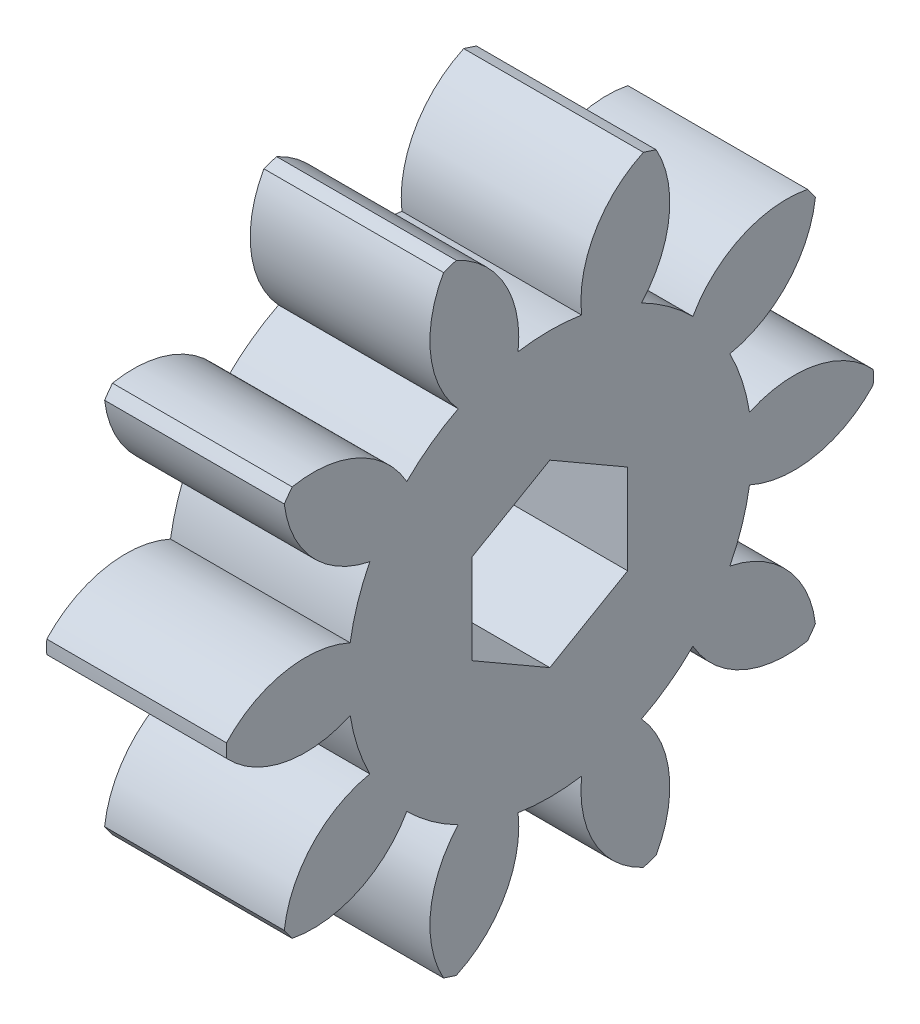
SolidWorks part; units mm, degrees
ref_plane "Plane1" through (0, 0, 0) normal (0, 0, 1) x (1, 0, 0)
ref_plane "Plane2" through (0, 0, 0) normal (0, 1, 0) x (1, 0, 0)
ref_plane "Plane3" through (0, 0, 0) normal (1, 0, 0) x (0, 0, -1)
sketch "HoldingSke" plane through (0, 0, 0) normal (0, 1, 0) x (1, 0, 0)
  line L0 (0, 0) -> (0.6565, -0.1158)
  line L1 (-15, 0) -> (100, 0) construction
  line L2 (0, 0) -> (-2.1039, 2.3779)
  line L3 (0, 0) -> (-11.863, 4.5341)
  line L4 (0, 0) -> (8.5048, 1.4996)
  line L5 (0, 0) -> (-46.8476, -17.4728)
  line L6 (0, 0) -> (-9.9476, -6.7116)
  line L7 (-2.1039, 2.3779) -> (8.6586, 51.206)
  line L8 (-76.2, 54.61) -> (-75.3, 54.61)
  line L9 (-71.009, 38.7566) -> (-53.1078, 45.2721)
  line L10 (-76.2, 71.12) -> (104.1128, 71.12)
  line L11 (0, 0) -> (-12, 0)
  line L12 (-76.2, 101.6) -> (-76.147, 101.6)
  line L13 (24.9733, 27.94) -> (52.9518, 28.4284)
  line L14 (24.9733, 27.94) -> (24.9743, 27.94)
  line L15 (24.9733, 27.94) -> (100.4006, 29.5858)
  line L16 (-63.627, -1.5) -> (-12.827, -1.5)
  circle A0 centre (0, 0) radius 2.5
  circle A1 centre (0, 0) radius 5.624
  circle A2 centre (0, 0) radius 37.5
  circle A3 centre (0, 0) radius 2.5
  dimension "MHD" = 11.248
  dimension "Hub_dia" = 75
  dimension "Bore" = 5
  dimension "MBD" = 5
  dimension "Num_teeth" = 10
  dimension "Pitch" = 0.6667
  dimension "Overall_len" = 50
  dimension "Show_teeth" = 10
  dimension "Thickness" = 12
  dimension "OAL" = 50.0002
  dimension "T_dim" = 0.9
  dimension "Ap" = 20
  dimension "H" = 19.05
  dimension "Pitch_radius" = 180.3128
  dimension "Width" = 12
  dimension "Backlash" = 0.053
  dimension "Addendum_fac" = 1
  dimension "Dedendum_fac" = 1.25
  dimension "Clearance_fac" = 0.25
  dimension "Dedendum_add" = 0.001
  dimension "Module" = 1.5
sketch "BasProSke" plane through (0, 0, 0) normal (0, 1, 0) x (1, 0, 0)
  line L0 (-10, 0) -> (60, 0) construction
  line L1 (0, 0) -> (0, 9)
  line L2 (0, 0) -> (5, 0)
  line L3 (5, 0) -> (5, 9)
  line L4 (5, 9) -> (0, 9)
  dimension "Thickness" = 5
  dimension "Diameter" = 18
revolve "Base-Revolve" add sketch "BasProSke" angle 360 about L0
sketch "TooCutSke" plane through (0, 0, 0) normal (1, 0, 0) x (0, 0, -1)
  line L1 (0, 0) -> (0, 107) construction
  line L2 (0, 0) -> (-1.2658, 7.3924) construction
  line L3 (0, 0) -> (-4.5869, 14.117) construction
  line L4 (-1.2658, 7.3924) -> (-2.2934, 7.0585) construction
  arc A0 (0.8839, 5.5541) -> (-0.8839, 5.5541) centre (0, 0) ccw
  arc A1 (2.6378, 8.6313) -> (-2.6378, 8.6313) centre (0, 0) ccw
  circle A2 centre (0, 0) radius 7.5 construction
  circle A3 centre (0, 0) radius 7.0477 construction
  arc A4 (-0.8839, 5.5541) -> (-2.6378, 8.6313) centre (-3.8646, 5.8936) ccw
  arc A5 (2.6378, 8.6313) -> (0.8839, 5.5541) centre (3.8646, 5.8936) ccw
  dimension "Root_dia" = 11.248
  dimension "Overcut_dia" = 18.0508
  dimension "Pitch_dia" = 15
  dimension "Base_dia" = 14.0954
  dimension "Flank_rad" = 3
  dimension "Half_ang" = 18
  dimension "Half_CT" = 1.0805
extrude "ToothCut" cut sketch "TooCutSke" along normal through all
fillet "Breaks" [suppressed] radius 0.03 tangent propagation no
fillet "RootFillets" [suppressed] radius 0.376
pattern_circular "TeethCuts" count 10 every 36 about axis through (-10, 0, 0) along (1, 0, 0) of "ToothCut", "RootFillets", "Breaks"
sketch "HubNeaOneSke" plane through (0, 0, 0) normal (-1, 0, 0) x (0, 0, 1)
  circle A0 centre (0, 0) radius 5.624
  dimension "Diameter" = 11.248
extrude "HubNearOne" [suppressed] add sketch "HubNeaOneSke" along normal blind 45.0002
sketch "HubNeaBotSke" plane through (0, 0, 0) normal (-1, 0, 0) x (0, 0, 1)
  circle A0 centre (0, 0) radius 5.624
  dimension "Diameter" = 11.248
extrude "HubNearBoth" [suppressed] add sketch "HubNeaBotSke" along normal blind 22.5001
ref_plane "FarPln" through (5, 0, 0) normal (1, 0, 0) x (0, 0, -1)
sketch "HubFarSke" plane through (5, 0, 0) normal (1, 0, 0) x (0, 0, -1)
  circle A0 centre (0, 0) radius 5.624
  dimension "Diameter" = 11.248
extrude "HubFar" [suppressed] add sketch "HubFarSke" along normal blind 22.5001
sketch "BorSke" plane through (0, 0, 0) normal (1, 0, 0) x (0, 0, -1)
  line L1 (0, 2.5) -> (-2.1651, 1.25)
  line L2 (-2.1651, 1.25) -> (-2.1651, -1.25)
  line L3 (-2.1651, -1.25) -> (0, -2.5)
  line L4 (0, -2.5) -> (2.1651, -1.25)
  line L5 (2.1651, -1.25) -> (2.1651, 1.25)
  line L6 (2.1651, 1.25) -> (0, 2.5)
  circle A0 centre (0, 0) radius 2.5 construction
  circle A1 centre (0, 0) radius 2.1651 construction
  point P2 (-0.1277, 3.0777)
  point P11 (0, 2.5)
  dimension "Diameter" = 5
extrude "Bore" cut sketch "BorSke" along normal mid plane 100.0004
sketch "KeySke" plane through (0, 0, 0) normal (1, 0, 0) x (0, 0, -1)
  line L0 (-1, 0) -> (-1, 3.4)
  line L1 (-1, 3.4) -> (1, 3.4)
  line L2 (1, 3.4) -> (1, 0)
  line L3 (0, 0) -> (0, 34) construction
  line L4 (-1, 0) -> (1, 0)
  dimension "Offset" = 3.4
  dimension "Width" = 2
extrude "Keyway" [suppressed] cut sketch "KeySke" along normal mid plane 100.0004
pattern_circular "Keyway2" [suppressed] count 2 every 90 about axis through (-10, 0, 0) along (1, 0, 0) reverse direction yes
equation "' \"Module@HoldingSke\" = 6.35"
equation "' \"Num_teeth@HoldingSke\" = 12"
equation "' \"Ap@HoldingSke\" =  20"
equation "' \"Ap@HoldingSke\" = 20"
equation "' \"Width@HoldingSke\" = 0.5 * 25.4"
equation "' \"Hub_dia@HoldingSke\"= 1 * 25.4"
equation "' \"Hub_dia@HoldingSke\" = 1 * 25.4"
equation "' \"Overall_len@HoldingSke\" = 1.0 * 25.4"
equation "' \"Bore@HoldingSke\" = 0.75 * 25.4"
equation "' \"T_dim@HoldingSke\" = 0.1 * 25.4"
equation "' \"Width@KeySke\" = 0.25 * 25.4"
equation "' \"Show_teeth@HoldingSke\" = 13"
equation "' \"Backlash@HoldingSke\" = 0.009 * 25.4"
equation "' \"Addendum_fac@HoldingSke\" = 1.0"
equation "' \"Dedendum_fac@HoldingSke\" = 1.25"
equation "' \"Dedendum_add@HoldingSke\" = 0.00005 * 25.4"
equation "' \"Clearance_fac@HoldingSke\" = 0.25"
equation "\"Pitch@HoldingSke\" = 1 / \"Module@HoldingSke\""
equation "\"Overcut_dia@TooCutSke\" = (\"Num_teeth@HoldingSke\" + 2 * \"Addendum_fac@HoldingSke\") / \"Pitch@HoldingSke\" + 0.002 * 25.4"
equation "\"Pitch_dia@TooCutSke\" = \"Num_teeth@HoldingSke\" / \"Pitch@HoldingSke\""
equation "\"Base_dia@TooCutSke\" = \"Num_teeth@HoldingSke\" / \"Pitch@HoldingSke\" * cos((\"Ap@HoldingSke\"  * 3.14159265 / 180))"
equation "\"Root_dia@TooCutSke\" = (\"Num_teeth@HoldingSke\" + 2) / \"Pitch@HoldingSke\" - 2 * (\"Addendum_fac@HoldingSke\" + \"Dedendum_fac@HoldingSke\") / \"Pitch@HoldingSke\" - \"Dedendum_add@HoldingSke\" * 2"
equation "\"Half_ang@TooCutSke\" = 180 / \"Num_teeth@HoldingSke\""
equation "\"Half_CT@TooCutSke\" = \"Num_teeth@HoldingSke\" / \"Pitch@HoldingSke\" * sin((3.14159265 / 2 / \"Num_teeth@HoldingSke\")) / 2 - 7 * \"Backlash@HoldingSke\" / 4"
equation "\"Flank_rad@TooCutSke\" = \"Num_teeth@HoldingSke\" / \"Pitch@HoldingSke\" / 5"
equation "\"Radius@RootFillets\" = \"Clearance_fac@HoldingSke\" / \"Pitch@HoldingSke\" + \"Dedendum_add@HoldingSke\""
equation "\"Break_rad@Breaks\" = 0.02 / \"Pitch@HoldingSke\""
equation "\"Thickness@HoldingSke\" = \"Width@HoldingSke\""
equation "\"OAL@HoldingSke\" = \"Thickness@HoldingSke\""
equation "\"MHD@HoldingSke\" = (\"Num_teeth@HoldingSke\" + 2) / \"Pitch@HoldingSke\" - 2 * (\"Addendum_fac@HoldingSke\" + \"Dedendum_fac@HoldingSke\")  / \"Pitch@HoldingSke\" - \"Dedendum_add@HoldingSke\" * 2"
equation "\"MBD@HoldingSke\" = (\"Num_teeth@HoldingSke\" + 2) / \"Pitch@HoldingSke\" - 2 * (\"Addendum_fac@HoldingSke\" + \"Dedendum_fac@HoldingSke\")  / \"Pitch@HoldingSke\" - \"Dedendum_add@HoldingSke\" * 2 - 0.002 * 25.4"
equation "\"MHD@HoldingSke\" = ((sgn( \"MHD@HoldingSke\" - \"Hub_dia@HoldingSke\" )-1)*( \"MHD@HoldingSke\" - \"Hub_dia@HoldingSke\" ))/-2+ \"Hub_dia@HoldingSke\""
equation "\"MBD@HoldingSke\" = ((sgn( \"MBD@HoldingSke\" - \"Bore@HoldingSke\" )-1)*( \"MBD@HoldingSke\" - \"Bore@HoldingSke\" ))/-2+ \"Bore@HoldingSke\""
equation "\"OAL@HoldingSke\" = ((sgn( \"OAL@HoldingSke\" - \"Overall_len@HoldingSke\" )+1)*( \"OAL@HoldingSke\" - \"Overall_len@HoldingSke\" ))/2 + \"Overall_len@HoldingSke\" + 0.000002 * 25.4"
equation "\"Num_teeth@TeethCuts\" = int( \"Show_teeth@HoldingSke\" ) + 1"
equation "\"Num_teeth@TeethCuts\" = ((sgn( \"Num_teeth@TeethCuts\" - \"Num_teeth@HoldingSke\" )-1)*( \"Num_teeth@TeethCuts\" - \"Num_teeth@HoldingSke\" ))/-2+ \"Num_teeth@HoldingSke\""
equation "\"Num_teeth@TeethCuts\" = ((sgn( \"Num_teeth@TeethCuts\" - 2.0)+1)*( \"Num_teeth@TeethCuts\" - 2.0))/2 +2.0"
equation "\"Angle@TeethCuts\" = 360.0 / \"Num_teeth@HoldingSke\""
equation "\"Diameter@BasProSke\" = (\"Num_teeth@HoldingSke\" + 2 * \"Addendum_fac@HoldingSke\") / \"Pitch@HoldingSke\""
equation "' \"Fillet_rad@BasProSke\" =  \"Thickness@HoldingSke\" * 0.05"
equation "' \"Fillet_rad@BasProSke\" = \"Thickness@HoldingSke\" * 0.05"
equation "\"MHD@HoldingSke\" = ((sgn( \"MHD@HoldingSke\" - \"Root_dia@TooCutSke\" )-1)*( \"MHD@HoldingSke\" - \"Root_dia@TooCutSke\" ))/-2+ \"Root_dia@TooCutSke\""
equation "\"Diameter@HubNeaOneSke\" = \"MHD@HoldingSke\""
equation "\"Length@HubNearOne\" = \"OAL@HoldingSke\" - \"Thickness@BasProSke\""
equation "\"Diameter@HubNeaBotSke\" = \"MHD@HoldingSke\""
equation "\"Length@HubNearBoth\" = ( \"OAL@HoldingSke\" - \"Thickness@BasProSke\" ) / 2.0"
equation "\"Thickness@FarPln\" = \"Thickness@BasProSke\""
equation "\"Diameter@HubFarSke\" = \"MHD@HoldingSke\""
equation "\"Length@HubFar\" = ( \"OAL@HoldingSke\" - \"Thickness@BasProSke\" ) / 2.0"
equation "\"Diameter@BorSke\" = \"MBD@HoldingSke\""
equation "\"D1@Bore\" = \"OAL@HoldingSke\" * 2.0"
equation "\"D1@Keyway\" = \"OAL@HoldingSke\" * 2.0"
equation "\"Offset@KeySke\" = \"T_dim@HoldingSke\" + \"MBD@HoldingSke\" / 2.0"
